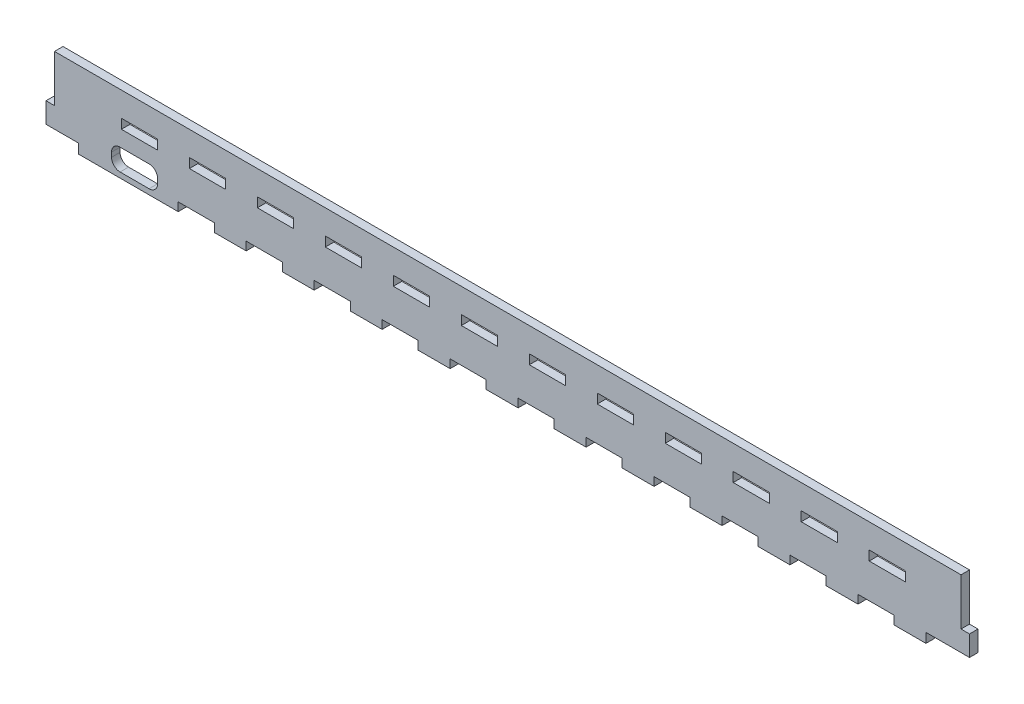
SolidWorks part; units mm, degrees
ref_plane "Plan de face" through (0, 0, 0) normal (0, 0, 1) x (1, 0, 0)
ref_plane "Plan de dessus" through (0, 0, 0) normal (0, 1, 0) x (1, 0, 0)
ref_plane "Plan de droite" through (0, 0, 0) normal (1, 0, 0) x (0, 0, -1)
sketch "Esquisse1" plane through (0, 0, 0) normal (0, 0, 1) x (1, 0, 0)
  line L1 (-108.68, -6.055) -> (108.68, -6.055)
  line L2 (-108.68, -6.055) -> (-108.68, 6.055)
  line L3 (-108.68, 6.055) -> (108.68, 6.055)
  line L4 (108.68, -6.055) -> (108.68, 6.055)
  line L5 (-108.68, -6.055) -> (108.68, 6.055) construction
  line L6 (-108.68, 6.055) -> (108.68, -6.055) construction
  point P0 (0, 0)
extrude "Boss.-Extru.1" add sketch "Esquisse1" along normal blind 2
sketch "Esquisse2" plane through (0, 0, 2) normal (0, 0, 1) x (1, 0, 0)
  line L1 (-109.57, -4.055) -> (-108.68, -4.055)
  line L2 (-109.57, -4.055) -> (-109.57, -6.055)
  line L3 (-109.57, -6.055) -> (-101.07, -6.055)
  line L4 (-101.07, -4.055) -> (-101.07, -6.055)
  line L5 (-90.93, 4.055) -> (-82.43, 4.055)
  line L6 (-90.93, 4.055) -> (-90.93, 6.055)
  line L7 (-90.93, 6.055) -> (-82.43, 6.055)
  line L8 (-82.43, 4.055) -> (-82.43, 6.055)
  line L9 (-108.68, -4.055) -> (-101.32, -4.055) construction
  line L10 (-101.32, -6.055) -> (-108.68, -6.055) construction
  line L12 (-90.68, 4.055) -> (-82.68, 4.055) construction
  line L13 (-90.68, 6.055) -> (-82.68, 6.055) construction
  line L22 (-77.57, -4.055) -> (-69.07, -4.055)
  line L23 (-77.57, -4.055) -> (-77.57, -6.055)
  line L24 (-77.57, -6.055) -> (-69.07, -6.055)
  line L25 (-69.07, -4.055) -> (-69.07, -6.055)
  line L30 (-61.57, -4.055) -> (-53.07, -4.055)
  line L31 (-61.57, -4.055) -> (-61.57, -6.055)
  line L32 (-61.57, -6.055) -> (-53.07, -6.055)
  line L33 (-53.07, -4.055) -> (-53.07, -6.055)
  line L38 (-45.57, -4.055) -> (-37.07, -4.055)
  line L39 (-45.57, -4.055) -> (-45.57, -6.055)
  line L40 (-45.57, -6.055) -> (-37.07, -6.055)
  line L41 (-37.07, -4.055) -> (-37.07, -6.055)
  line L46 (-29.57, -4.055) -> (-21.07, -4.055)
  line L47 (-29.57, -4.055) -> (-29.57, -6.055)
  line L48 (-29.57, -6.055) -> (-21.07, -6.055)
  line L49 (-21.07, -4.055) -> (-21.07, -6.055)
  line L54 (-13.57, -4.055) -> (-5.07, -4.055)
  line L55 (-13.57, -4.055) -> (-13.57, -6.055)
  line L56 (-13.57, -6.055) -> (-5.07, -6.055)
  line L57 (-5.07, -4.055) -> (-5.07, -6.055)
  line L62 (2.43, -4.055) -> (10.93, -4.055)
  line L63 (2.43, -4.055) -> (2.43, -6.055)
  line L64 (2.43, -6.055) -> (10.93, -6.055)
  line L65 (10.93, -4.055) -> (10.93, -6.055)
  line L70 (18.43, -4.055) -> (26.93, -4.055)
  line L71 (18.43, -4.055) -> (18.43, -6.055)
  line L72 (18.43, -6.055) -> (26.93, -6.055)
  line L73 (26.93, -4.055) -> (26.93, -6.055)
  line L78 (34.43, -4.055) -> (42.93, -4.055)
  line L79 (34.43, -4.055) -> (34.43, -6.055)
  line L80 (34.43, -6.055) -> (42.93, -6.055)
  line L81 (42.93, -4.055) -> (42.93, -6.055)
  line L86 (50.43, -4.055) -> (58.93, -4.055)
  line L87 (50.43, -4.055) -> (50.43, -6.055)
  line L88 (50.43, -6.055) -> (58.93, -6.055)
  line L89 (58.93, -4.055) -> (58.93, -6.055)
  line L94 (66.43, -4.055) -> (74.93, -4.055)
  line L95 (66.43, -4.055) -> (66.43, -6.055)
  line L96 (66.43, -6.055) -> (74.93, -6.055)
  line L97 (74.93, -4.055) -> (74.93, -6.055)
  line L102 (82.43, -4.055) -> (90.93, -4.055)
  line L103 (82.43, -4.055) -> (82.43, -6.055)
  line L104 (82.43, -6.055) -> (90.93, -6.055)
  line L105 (90.93, -4.055) -> (90.93, -6.055)
  line L110 (101.07, 4.055) -> (109.57, 4.055) [skipped]
  line L111 (101.07, 4.055) -> (101.07, 6.055) [skipped]
  line L112 (101.07, 6.055) -> (109.57, 6.055) [skipped]
  line L113 (109.57, 4.055) -> (109.57, 6.055) [skipped]
  line L114 (-77.32, -6.055) -> (-77.32, -4.055) construction
  line L115 (-69.32, -4.055) -> (-69.32, -6.055) construction
  line L117 (-74.93, 4.055) -> (-66.43, 4.055) [skipped]
  line L118 (-74.93, 4.055) -> (-74.93, 6.055) [skipped]
  line L119 (-74.93, 6.055) -> (-66.43, 6.055) [skipped]
  line L120 (-66.43, 4.055) -> (-66.43, 6.055) [skipped]
  line L121 (-58.93, 4.055) -> (-50.43, 4.055) [skipped]
  line L122 (-58.93, 4.055) -> (-58.93, 6.055) [skipped]
  line L123 (-58.93, 6.055) -> (-50.43, 6.055) [skipped]
  line L124 (-50.43, 4.055) -> (-50.43, 6.055) [skipped]
  line L125 (-42.93, 4.055) -> (-34.43, 4.055) [skipped]
  line L126 (-42.93, 4.055) -> (-42.93, 6.055) [skipped]
  line L127 (-42.93, 6.055) -> (-34.43, 6.055) [skipped]
  line L128 (-34.43, 4.055) -> (-34.43, 6.055) [skipped]
  line L129 (-26.93, 4.055) -> (-18.43, 4.055) [skipped]
  line L130 (-26.93, 4.055) -> (-26.93, 6.055) [skipped]
  line L131 (-26.93, 6.055) -> (-18.43, 6.055) [skipped]
  line L132 (-18.43, 4.055) -> (-18.43, 6.055) [skipped]
  line L133 (-10.93, 4.055) -> (-2.43, 4.055) [skipped]
  line L134 (-10.93, 4.055) -> (-10.93, 6.055) [skipped]
  line L135 (-10.93, 6.055) -> (-2.43, 6.055) [skipped]
  line L136 (-2.43, 4.055) -> (-2.43, 6.055) [skipped]
  line L137 (5.07, 4.055) -> (13.57, 4.055) [skipped]
  line L138 (5.07, 4.055) -> (5.07, 6.055) [skipped]
  line L139 (5.07, 6.055) -> (13.57, 6.055) [skipped]
  line L140 (13.57, 4.055) -> (13.57, 6.055) [skipped]
  line L141 (21.07, 4.055) -> (29.57, 4.055) [skipped]
  line L142 (21.07, 4.055) -> (21.07, 6.055) [skipped]
  line L143 (21.07, 6.055) -> (29.57, 6.055) [skipped]
  line L144 (29.57, 4.055) -> (29.57, 6.055) [skipped]
  line L145 (37.07, 4.055) -> (45.57, 4.055) [skipped]
  line L146 (37.07, 4.055) -> (37.07, 6.055) [skipped]
  line L147 (37.07, 6.055) -> (45.57, 6.055) [skipped]
  line L148 (45.57, 4.055) -> (45.57, 6.055) [skipped]
  line L149 (53.07, 4.055) -> (61.57, 4.055) [skipped]
  line L150 (53.07, 4.055) -> (53.07, 6.055) [skipped]
  line L151 (53.07, 6.055) -> (61.57, 6.055) [skipped]
  line L152 (61.57, 4.055) -> (61.57, 6.055) [skipped]
  line L153 (69.07, 4.055) -> (77.57, 4.055) [skipped]
  line L154 (69.07, 4.055) -> (69.07, 6.055) [skipped]
  line L155 (69.07, 6.055) -> (77.57, 6.055) [skipped]
  line L156 (77.57, 4.055) -> (77.57, 6.055) [skipped]
  line L157 (85.07, 4.055) -> (93.57, 4.055) [skipped]
  line L158 (85.07, 4.055) -> (85.07, 6.055) [skipped]
  line L159 (85.07, 6.055) -> (93.57, 6.055) [skipped]
  line L160 (93.57, 4.055) -> (93.57, 6.055) [skipped]
  line L161 (-82.68, 4.055) -> (-82.68, 6.055) construction
  line L162 (-74.93, 4.055) -> (-66.43, 4.055)
  line L163 (-74.93, 4.055) -> (-74.93, 6.055)
  line L164 (-74.93, 6.055) -> (-66.43, 6.055)
  line L165 (-66.43, 4.055) -> (-66.43, 6.055)
  line L166 (-58.93, 4.055) -> (-50.43, 4.055)
  line L167 (-58.93, 4.055) -> (-58.93, 6.055)
  line L168 (-58.93, 6.055) -> (-50.43, 6.055)
  line L169 (-50.43, 4.055) -> (-50.43, 6.055)
  line L170 (-42.93, 4.055) -> (-34.43, 4.055)
  line L171 (-42.93, 4.055) -> (-42.93, 6.055)
  line L172 (-42.93, 6.055) -> (-34.43, 6.055)
  line L173 (-34.43, 4.055) -> (-34.43, 6.055)
  line L174 (-26.93, 4.055) -> (-18.43, 4.055)
  line L175 (-26.93, 4.055) -> (-26.93, 6.055)
  line L176 (-26.93, 6.055) -> (-18.43, 6.055)
  line L177 (-18.43, 4.055) -> (-18.43, 6.055)
  line L178 (-10.93, 4.055) -> (-2.43, 4.055)
  line L179 (-10.93, 4.055) -> (-10.93, 6.055)
  line L180 (-10.93, 6.055) -> (-2.43, 6.055)
  line L181 (-2.43, 4.055) -> (-2.43, 6.055)
  line L182 (5.07, 4.055) -> (13.57, 4.055)
  line L183 (5.07, 4.055) -> (5.07, 6.055)
  line L184 (5.07, 6.055) -> (13.57, 6.055)
  line L185 (13.57, 4.055) -> (13.57, 6.055)
  line L186 (21.07, 4.055) -> (29.57, 4.055)
  line L187 (21.07, 4.055) -> (21.07, 6.055)
  line L188 (21.07, 6.055) -> (29.57, 6.055)
  line L189 (29.57, 4.055) -> (29.57, 6.055)
  line L190 (37.07, 4.055) -> (45.57, 4.055)
  line L191 (37.07, 4.055) -> (37.07, 6.055)
  line L192 (37.07, 6.055) -> (45.57, 6.055)
  line L193 (45.57, 4.055) -> (45.57, 6.055)
  line L194 (53.07, 4.055) -> (61.57, 4.055)
  line L195 (53.07, 4.055) -> (53.07, 6.055)
  line L196 (53.07, 6.055) -> (61.57, 6.055)
  line L197 (61.57, 4.055) -> (61.57, 6.055)
  line L198 (69.07, 4.055) -> (77.57, 4.055)
  line L199 (69.07, 4.055) -> (69.07, 6.055)
  line L200 (69.07, 6.055) -> (77.57, 6.055)
  line L201 (77.57, 4.055) -> (77.57, 6.055)
  line L202 (85.07, 4.055) -> (93.57, 4.055)
  line L203 (85.07, 4.055) -> (85.07, 6.055)
  line L204 (85.07, 6.055) -> (93.57, 6.055)
  line L205 (93.57, 4.055) -> (93.57, 6.055)
  line L206 (93.32, 4.055) -> (93.32, 6.055) construction
  line L207 (90.68, -4.055) -> (90.68, -6.055) construction
  line L208 (82.68, -4.055) -> (90.68, -4.055) construction
  line L209 (-108.68, -6.055) -> (108.68, -6.055) construction
  line L210 (98.43, -6.055) -> (108.68, -6.055)
  line L211 (98.43, -6.055) -> (98.43, -3.805)
  line L212 (98.43, -3.805) -> (108.68, -3.805)
  line L213 (108.68, -6.055) -> (108.68, -3.805)
  line L214 (108.68, -6.055) -> (108.68, 6.055) construction
  line L215 (108.68, -4.055) -> (98.68, -4.055) construction
  line L216 (98.68, -6.055) -> (98.68, -4.055) construction
  line L218 (-108.68, -4.055) -> (-101.07, -4.055) construction
  line L219 (-108.68, -4.055) -> (-108.68, -3.805)
  line L220 (-108.68, -3.805) -> (-101.07, -3.805)
  line L221 (-101.07, -4.055) -> (-101.07, -3.805)
  line L223 (-108.68, -4.055) -> (-101.07, -4.055) construction
  line L224 (-93.57, -4.055) -> (-85.07, -4.055) [skipped]
  line L225 (-93.57, -4.055) -> (-93.57, -6.055) [skipped]
  line L226 (-93.57, -6.055) -> (-85.07, -6.055) [skipped]
  line L227 (-85.07, -4.055) -> (-85.07, -6.055) [skipped]
  point P3 (-89, -4.055)
  point P8 (-105, -4.055)
  point P17 (-86.68, 4.055)
  point P24 (105.32, 4.055)
  point P28 (89.32, 4.055)
  point P29 (73.32, 4.055)
  point P30 (57.32, 4.055)
  point P31 (41.32, 4.055)
  point P38 (25.32, 4.055)
  point P39 (9.32, 4.055)
  point P40 (-6.68, 4.055)
  point P41 (-22.68, 4.055)
  point P42 (-73, -4.055)
  point P43 (-70.68, 4.055)
  point P48 (-38.68, 4.055)
  point P49 (-54.68, 4.055)
  point P52 (-57, -4.055)
  point P58 (-70.68, 4.055)
  point P62 (-41, -4.055)
  point P68 (-54.68, 4.055)
  point P72 (-25, -4.055)
  point P78 (-38.68, 4.055)
  point P82 (-9, -4.055)
  point P88 (-22.68, 4.055)
  point P92 (7, -4.055)
  point P98 (-6.68, 4.055)
  point P102 (23, -4.055)
  point P108 (9.32, 4.055)
  point P112 (39, -4.055)
  point P118 (25.32, 4.055)
  point P122 (55, -4.055)
  point P128 (41.32, 4.055)
  point P132 (71, -4.055)
  point P141 (57.32, 4.055)
  point P142 (87, -4.055)
  point P243 (73.32, 4.055)
  point P248 (89.32, 4.055)
  dimension "D1" = 0.25
  dimension "D2" = 0.25
  dimension "D4" = 0.25
  dimension "D6" = 0.25
  dimension "D7" = 0.25
  dimension "D8" = 0.25
  dimension "D9" = 0.25
  dimension "D10" = 0.25
  dimension "D3" = 13
  dimension "D5" = 12
extrude "Enlèv. mat.-Extru.1" cut sketch "Esquisse2" against normal through all
sketch "Esquisse3" plane through (0, 0, 2) normal (0, 0, 1) x (1, 0, 0)
  line L0 (-93.002, -1.925) -> (-93.002, -2.625) construction
  line L1 (-91.252, 0.255) -> (-84.412, 0.255)
  line L2 (-93.252, -1.745) -> (-93.252, -2.805)
  line L3 (-91.252, -4.805) -> (-84.412, -4.805)
  line L4 (-82.412, -1.745) -> (-82.412, -2.805)
  line L5 (-82.662, -2.625) -> (-82.662, -1.925) construction
  line L6 (-84.592, 0.005) -> (-91.072, 0.005) construction
  line L7 (-91.072, -4.555) -> (-84.592, -4.555) construction
  arc A0 (-93.252, -2.805) -> (-91.252, -4.805) centre (-91.252, -2.805) ccw
  arc A1 (-84.412, 0.255) -> (-82.412, -1.745) centre (-84.412, -1.745) cw
  arc A2 (-84.412, -4.805) -> (-82.412, -2.805) centre (-84.412, -2.805) ccw
  arc A3 (-91.252, 0.255) -> (-93.252, -1.745) centre (-91.252, -1.745) ccw
  dimension "D5" = 2
  dimension "D1" = 0.25
  dimension "D2" = 0.25
  dimension "D3" = 0.25
  dimension "D4" = 0.25
extrude "Enlèv. mat.-Extru.2" cut sketch "Esquisse3" against normal through all
sketch "Esquisse5" plane through (0, 0, 2) normal (0, 0, 1) x (1, 0, 0)
  line L0 (0, 0) -> (0, -11.5957) construction
  line L1 (-108.68, 1) -> (-106.68, 1)
  line L2 (-108.68, 1) -> (-108.68, 6.055)
  line L3 (-108.68, 6.055) -> (-106.68, 6.055)
  line L4 (-106.68, 1) -> (-106.68, 6.055)
  line L5 (106.68, 1) -> (106.68, 6.055)
  line L6 (108.68, 6.055) -> (106.68, 6.055)
  line L7 (108.68, 1) -> (108.68, 6.055)
  line L8 (108.68, 1) -> (106.68, 1)
extrude "Enlèv. mat.-Extru.3" cut sketch "Esquisse5" against normal through all
sketch "Esquisse6" plane through (0, 0, 2) normal (0, 0, 1) x (1, 0, 0)
  line L1 (-106.68, 6.055) -> (106.68, 6.055)
  line L2 (-106.68, 6.055) -> (-106.68, 12.055)
  line L3 (-106.68, 12.055) -> (106.68, 12.055)
  line L4 (106.68, 6.055) -> (106.68, 12.055)
extrude "Boss.-Extru.2" add sketch "Esquisse6" against normal up to surface (2 mm away) up to face at (3.3846, 0.0865, 0)
sketch "Esquisse7" plane through (0, 0, 2) normal (0, 0, 1) x (1, 0, 0)
  line L0 (-74.93, 6.055) -> (-66.43, 6.055)
  line L1 (-90.93, 6.055) -> (-82.43, 6.055)
  line L2 (-90.93, 6.055) -> (-90.93, 6.305)
  line L3 (-90.93, 6.305) -> (-82.43, 6.305)
  line L4 (-82.43, 6.055) -> (-82.43, 6.305)
  line L5 (-74.93, 6.055) -> (-74.93, 6.305)
  line L6 (-74.93, 6.305) -> (-66.43, 6.305)
  line L7 (-66.43, 6.055) -> (-66.43, 6.305)
  line L8 (-58.93, 6.055) -> (-50.43, 6.055)
  line L9 (-58.93, 6.055) -> (-58.93, 6.305)
  line L10 (-58.93, 6.305) -> (-50.43, 6.305)
  line L11 (-50.43, 6.055) -> (-50.43, 6.305)
  line L12 (-42.93, 6.055) -> (-34.43, 6.055)
  line L13 (-42.93, 6.055) -> (-42.93, 6.305)
  line L14 (-42.93, 6.305) -> (-34.43, 6.305)
  line L15 (-34.43, 6.055) -> (-34.43, 6.305)
  line L16 (-26.93, 6.055) -> (-18.43, 6.055)
  line L17 (-26.93, 6.055) -> (-26.93, 6.305)
  line L18 (-26.93, 6.305) -> (-18.43, 6.305)
  line L19 (-18.43, 6.055) -> (-18.43, 6.305)
  line L20 (-10.93, 6.055) -> (-2.43, 6.055)
  line L21 (-10.93, 6.055) -> (-10.93, 6.305)
  line L22 (-10.93, 6.305) -> (-2.43, 6.305)
  line L23 (-2.43, 6.055) -> (-2.43, 6.305)
  line L24 (5.07, 6.055) -> (13.57, 6.055)
  line L25 (5.07, 6.055) -> (5.07, 6.305)
  line L26 (5.07, 6.305) -> (13.57, 6.305)
  line L27 (13.57, 6.055) -> (13.57, 6.305)
  line L28 (21.07, 6.055) -> (29.57, 6.055)
  line L29 (21.07, 6.055) -> (21.07, 6.305)
  line L30 (21.07, 6.305) -> (29.57, 6.305)
  line L31 (29.57, 6.055) -> (29.57, 6.305)
  line L32 (37.07, 6.055) -> (45.57, 6.055)
  line L33 (37.07, 6.055) -> (37.07, 6.305)
  line L34 (37.07, 6.305) -> (45.57, 6.305)
  line L35 (45.57, 6.055) -> (45.57, 6.305)
  line L36 (53.07, 6.055) -> (61.57, 6.055)
  line L37 (53.07, 6.055) -> (53.07, 6.305)
  line L38 (53.07, 6.305) -> (61.57, 6.305)
  line L39 (61.57, 6.055) -> (61.57, 6.305)
  line L40 (69.07, 6.055) -> (77.57, 6.055)
  line L41 (69.07, 6.055) -> (69.07, 6.305)
  line L42 (69.07, 6.305) -> (77.57, 6.305)
  line L43 (77.57, 6.055) -> (77.57, 6.305)
  line L44 (85.07, 6.055) -> (93.57, 6.055)
  line L45 (85.07, 6.055) -> (85.07, 6.305)
  line L46 (85.07, 6.305) -> (93.57, 6.305)
  line L47 (93.57, 6.055) -> (93.57, 6.305)
  line L48 (85.07, 6.055) -> (93.57, 6.055) construction
  dimension "D1" = 0.25
  dimension "D2" = 12
extrude "Enlèv. mat.-Extru.4" cut sketch "Esquisse7" against normal through all
